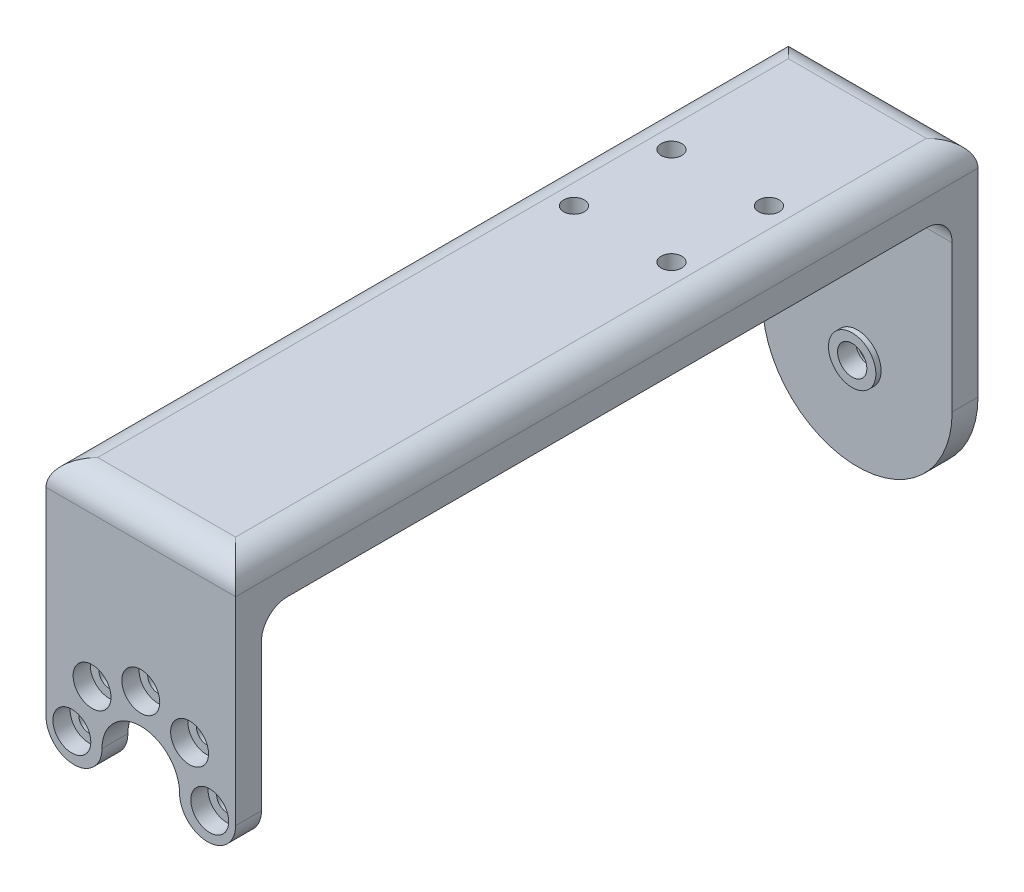
SolidWorks part; units mm, degrees
ref_plane "Plano frontal" through (0, 0, 0) normal (0, 0, 1) x (1, 0, 0)
ref_plane "Plano superior" through (0, 0, 0) normal (0, 1, 0) x (1, 0, 0)
ref_plane "Plano direito" through (0, 0, 0) normal (1, 0, 0) x (0, 0, -1)
sketch "Esboço1" plane through (0, 0, 0) normal (0, 0, 1) x (1, 0, 0)
  line L0 (11, 0) -> (11, 23)
  line L1 (11, 23) -> (-11, 23)
  line L2 (-11, 23) -> (-11, 0)
  arc A3 (11, 0) -> (4.5, 0) centre (7.75, 0) cw
  arc A8 (4.5, 0) -> (-4.5, 0) centre (0, 0) ccw
  arc A10 (-4.5, 0) -> (-11, 0) centre (-7.75, 0) cw
  dimension "D1" = 23
extrude "Ressalto-extrusão1" add sketch "Esboço1" along normal blind 3
sketch "Esboço2" plane through (0, 23, 0) normal (0, 1, 0) x (1, 0, 0)
  line L0 (11, -3) -> (11, 0) construction
  line L1 (-11, -3) -> (11, -3)
  line L2 (-11, -3) -> (-11, 83.15)
  line L3 (-11, 83.15) -> (11, 83.15)
  line L4 (11, -3) -> (11, 83.15)
  line L5 (11, -3) -> (-11, -3) construction
  point P7 (0, -3)
  point P8 (0, -3)
  dimension "D1" = 86.15
extrude "Ressalto-extrusão2" add sketch "Esboço2" along normal blind 3
ref_plane "Plano2" through (0, 0, -80.15) normal (0, 0, -1) x (-1, 0, 0)
sketch "Esboço3" plane through (0, 0, -80.15) normal (0, 0, -1) x (-1, 0, 0)
  line L1 (-11, 0) -> (-11, 23)
  line L2 (-11, 23) -> (11, 23)
  line L3 (11, 23) -> (11, 0)
  arc A0 (-11, 0) -> (11, 0) centre (0, 0) ccw
  dimension "D1" = 22
extrude "Ressalto-extrusão3" add sketch "Esboço3" along normal blind 3
hole_wizard "Rebaixo para SHCS M21" positions "Esboço4" profile "Esboço5" counterbore size "M2" standard "Ansi Metric" end condition up to next
sketch "Esboço4" plane through (0, 0, 3) normal (0, 0, 1) x (1, 0, 0)
  arc A0 (8.8, 0) -> (7.2, 0) centre (8, 0) ccw construction
  point P0 (8, 0)
sketch "Esboço5" plane through (8, 0, 3) normal (1, 0, 0) x (0, -1, 0)
  line L0 (0, 0) -> (0, 3)
  line L1 (0, 3) -> (1.2, 3)
  line L3 (1.2, 3) -> (1.2, 2)
  line L4 (1.2, 2) -> (2.2, 2)
  line L5 (2.2, 2) -> (2.2, 0)
  line L7 (2.2, 0) -> (0, 0)
  line L11 (0, -6.35) -> (0, 107.95) construction
  dimension "Thru Hole Dia." = 2.4
  dimension "Thru Hole Depth" = 3
  dimension "C'Bore Dia." = 4.4
  dimension "C'Bore Depth" = 2
pattern_circular "PadrãoCircular1" count 5 every 45 about axis through (0, 0, 3) along (0, 0, -1) of "Rebaixo para SHCS M21" reverse direction yes
sketch "Esboço10" plane through (0, 0, -80.15) normal (0, 0, 1) x (1, 0, 0)
  circle A0 centre (0, 0) radius 2.75
  circle A2 centre (0, 0) radius 3.25 construction
  dimension "D1" = 0.5
extrude "Ressalto-extrusão4" add sketch "Esboço10" along normal blind 0.6 contours A0
hole_wizard "Rebaixo para parafuso com cabeça panela de M31" positions "Esboço11" profile "Esboço12" counterbore size "M3" standard "DIN" end condition up to next
sketch "Esboço11" plane through (0, 0, -83.15) normal (0, 0, -1) x (-1, 0, 0)
  circle A0 centre (0, 0) radius 3.25 construction
  point P0 (0, 0)
sketch "Esboço12" plane through (0, 0, -83.15) normal (1, 0, 0) x (0, 1, 0)
  line L0 (0, 0) -> (0, 3.6)
  line L1 (0, 3.6) -> (1.7, 3.6)
  line L3 (1.7, 3.6) -> (1.7, 1.5)
  line L4 (1.7, 1.5) -> (3.5, 1.5)
  line L5 (3.5, 1.5) -> (3.5, 0)
  line L7 (3.5, 0) -> (0, 0)
  line L11 (0, -6.35) -> (0, 107.95) construction
  dimension "Thru Hole Dia." = 3.4
  dimension "Thru Hole Depth" = 3.6
  dimension "C'Bore Dia." = 7
  dimension "C'Bore Depth" = 1.5
ref_plane "Plano3" through (0, 0, -40.075) normal (0, 0, -1) x (-1, 0, 0)
sketch "Esboço14" plane through (-11, 0, 0) normal (-1, 0, 0) x (0, 0, 1)
  line L0 (3, 26) -> (3, 0) construction
  line L1 (-83.15, 26) -> (3, 26)
  line L2 (-83.15, 26) -> (-83.15, 20)
  line L3 (-83.15, 20) -> (3, 20)
  line L4 (3, 26) -> (3, 20)
  line L5 (-80.15, 23) -> (0, 23) construction
  dimension "D1" = 3
extrude "Ressalto-extrusão5" add sketch "Esboço14" against normal blind 3
mirror "Espelhar2" about plane through (0, 0, 0) normal (1, 0, 0) of "Ressalto-extrusão5"
hole_wizard "Rebaixo para parafuso com cabeça redonda de M21" positions "Esboço16" profile "Esboço17" counterbore size "M2" standard "DIN" end condition up to next
sketch "Esboço16" plane through (0, 23, 0) normal (0, -1, 0) x (-1, 0, 0)
  line L0 (0, 58.5796) -> (5.6569, 64.2364) construction
  line L2 (0, 58.5796) -> (25.8, 58.5796) construction
  line L3 (25.8, 67.0796) -> (25.8, 50.0796) construction
  line L4 (25.8, 67.0796) -> (25.8, 50.0796) construction
  line L5 (-11, 83.15) -> (11, 83.15) construction
  line L6 (0, 58.5796) -> (-5.6569, 52.9227) construction
  point P0 (5.6569, 64.2364)
  point P25 (5.6569, 52.9227)
  point P26 (-5.6569, 52.9227)
  point P27 (-5.6569, 64.2364)
  point P42 (0, 83.15)
  point P50 (-8.1871, 49.3629)
  point P51 (0, 0)
  dimension "D1" = 45
  dimension "D2" = 8
  dimension "D3" = 4
sketch "Esboço17" plane through (-5.6569, 23, -64.2364) normal (1, 0, 0) x (0, 0, -1)
  line L0 (0, 0) -> (0, 3)
  line L1 (0, 3) -> (1.2, 3)
  line L3 (1.2, 3) -> (1.2, 1)
  line L4 (1.2, 1) -> (2.2, 1)
  line L5 (2.2, 1) -> (2.2, 0)
  line L7 (2.2, 0) -> (0, 0)
  line L11 (0, -6.35) -> (0, 107.95) construction
  dimension "Thru Hole Dia." = 2.4
  dimension "Thru Hole Depth" = 3
  dimension "C'Bore Dia." = 4.4
  dimension "C'Bore Depth" = 1
fillet "Filete2" radius 3 4 edges at (9.5, 20, -80.15) (9.5, 20, 0) (-9.5, 20, -80.15) (-9.5, 20, 0)
fillet "Filete1" radius 3 8 edges at (8, 23, -40.075) (0, 23, -80.15) (-8, 23, -40.075) (0, 23, 0) (11, 26, -40.075) (0, 26, 3) (-11, 26, -40.075) (0, 26, -83.15)
